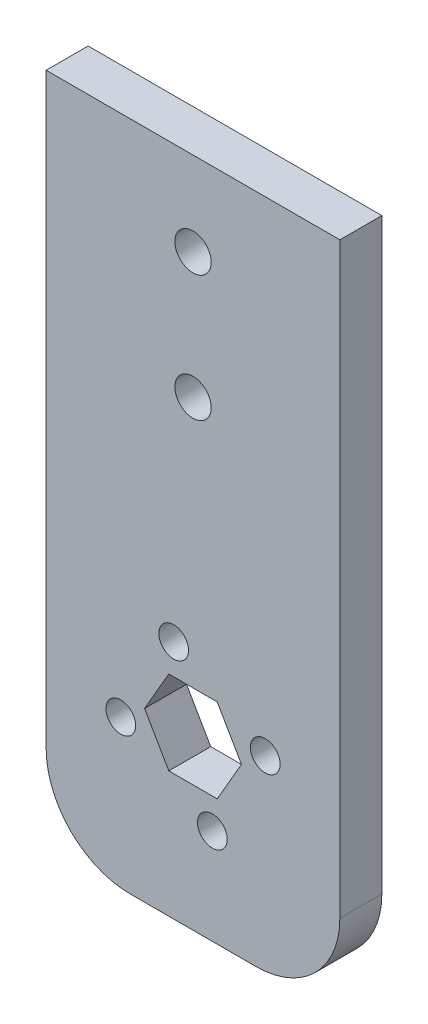
SolidWorks part; units mm, degrees
material "6061 Alloy"
ref_plane "Front Plane" through (0, 0, 0) normal (0, 0, 1) x (1, 0, 0)
ref_plane "Top Plane" through (0, 0, 0) normal (0, 1, 0) x (1, 0, 0)
ref_plane "Right Plane" through (0, 0, 0) normal (1, 0, 0) x (0, 0, -1)
sketch "Sketch1" plane through (0, 0, 0) normal (0, 0, 1) x (1, 0, 0)
  line L1 (0, 0) -> (-44.45, 0)
  line L2 (0, 0) -> (0, 101.6)
  line L3 (0, 101.6) -> (-44.45, 101.6)
  line L4 (-44.45, 0) -> (-44.45, 101.6)
  dimension "D1" = 101.6
  dimension "D2" = 44.45
extrude "Boss-Extrude2" add sketch "Sketch1" along normal blind 6.35
sketch "Sketch3" plane through (0, 0, 0) normal (0, 0, -1) x (-1, 0, 0)
  line L0 (22.225, 101.6) -> (22.225, 0) construction
  line L1 (0, 101.6) -> (44.45, 101.6) construction
  line L2 (44.45, 0) -> (0, 0) construction
  point P3 (22.225, 50.8)
fillet "Fillet1" radius 12.7 2 edges at (-44.45, 0, 3.175) (0, 0, 3.175)
hole_wizard "M5 Clearance Hole1" positions "Sketch11" profile "Sketch12" hole size "M5" standard "ANSI Metric" end condition through all
sketch "Sketch11" plane through (0, 0, 0) normal (0, 0, -1) x (-1, 0, 0)
  line L0 (22.225, 101.6) -> (22.225, 0) construction
  line L1 (0, 101.6) -> (44.45, 101.6) construction
  point P0 (22.225, 88.9)
  point P4 (22.225, 69.85)
  dimension "D1" = 19.05
  dimension "D2" = 12.7
sketch "Sketch12" plane through (-22.225, 88.9, 0) normal (1, 0, 0) x (0, 1, 0)
  line L0 (0, 0) -> (0, 6.35)
  line L1 (0, 6.35) -> (2.75, 6.35)
  line L2 (2.75, 6.35) -> (2.75, 0)
  line L5 (2.75, 0) -> (0, 0)
  line L11 (0, -6.35) -> (0, 107.95) construction
  dimension "Thru Hole Dia." = 5.5
  dimension "Thru Hole Depth" = 6.35
sketch "Sketch14" plane through (0, 0, 6.35) normal (0, 0, 1) x (1, 0, 0)
  line L0 (-22.225, 101.6) -> (-22.225, 0) construction
  line L1 (-14.8927, 25.4) -> (-18.5588, 31.75)
  line L2 (-18.5588, 31.75) -> (-25.8912, 31.75)
  line L3 (-25.8912, 31.75) -> (-29.5573, 25.4)
  line L4 (-29.5573, 25.4) -> (-25.8912, 19.05)
  line L5 (-25.8912, 19.05) -> (-18.5588, 19.05)
  line L6 (-18.5588, 19.05) -> (-14.8927, 25.4)
  line L7 (-31.75, 0) -> (-12.7, 0) construction
  circle A0 centre (-22.225, 25.4) radius 6.35 construction
  point P12 (-22.225, 31.75)
  dimension "D1" = 12.7
  dimension "D2" = 25.4
extrude "Cut-Extrude1" cut sketch "Sketch14" against normal through all
sketch "Sketch22" plane through (0, 0, 6.35) normal (0, 0, 1) x (1, 0, 0)
  circle A0 centre (-25.1532, 36.3282) radius 2.05
  circle A1 centre (-11.2968, 28.3282) radius 2.05
  circle A2 centre (-19.2968, 14.4718) radius 2.05
  circle A3 centre (-33.1532, 22.4718) radius 2.05
hole_wizard "M4 Clearance Hole1" positions "Sketch25" profile "Sketch24" hole size "M4" standard "ANSI Metric" end condition through all
sketch "Sketch25" plane through (0, 0, 0) normal (0, 0, -1) x (-1, 0, 0)
  point P0 (11.2968, 28.3282)
  point P3 (25.1532, 36.3282)
  point P6 (33.1532, 22.4718)
  point P9 (19.2968, 14.4718)
sketch "Sketch24" plane through (-11.2968, 28.3282, 0) normal (1, 0, 0) x (0, 1, 0)
  line L0 (0, 0) -> (0, 6.35)
  line L1 (0, 6.35) -> (2.25, 6.35)
  line L2 (2.25, 6.35) -> (2.25, 0)
  line L5 (2.25, 0) -> (0, 0)
  line L11 (0, -6.35) -> (0, 107.95) construction
  dimension "Thru Hole Dia." = 4.5
  dimension "Thru Hole Depth" = 6.35
